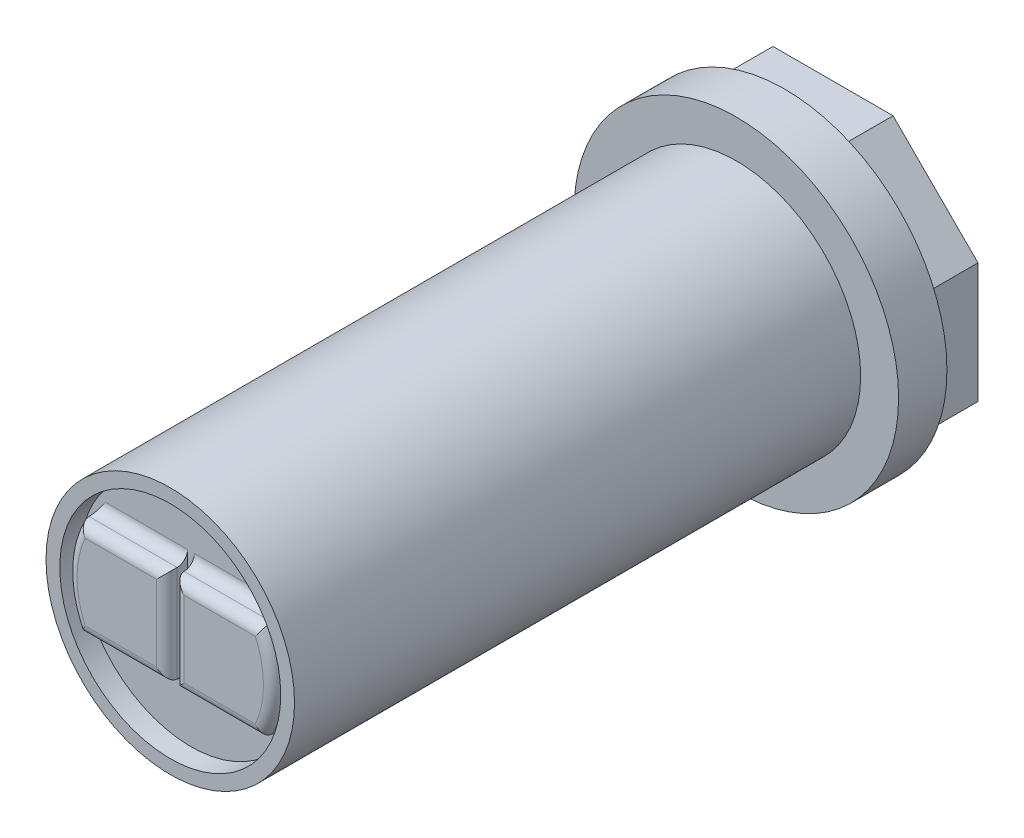
SolidWorks part; units mm, degrees
ref_plane "前视基准面" through (0, 0, 0) normal (0, 0, 1) x (1, 0, 0)
ref_plane "上视基准面" through (0, 0, 0) normal (0, 1, 0) x (1, 0, 0)
ref_plane "右视基准面" through (0, 0, 0) normal (1, 0, 0) x (0, 0, -1)
sketch "草图1" plane through (0, 0, 0) normal (0, 0, 1) x (1, 0, 0)
  circle A0 centre (0, 0) radius 9
  dimension "D1" = 18
extrude "凸台-拉伸1" add sketch "草图1" along normal blind 48
sketch "草图2" plane through (0, 0, 0) normal (0, 0, -1) x (-1, 0, 0)
  line L1 (-10.5, 4.3492) -> (-10.5, -4.3492)
  line L2 (-10.5, -4.3492) -> (-4.3492, -10.5)
  line L3 (-4.3492, -10.5) -> (4.3492, -10.5)
  line L4 (4.3492, -10.5) -> (10.5, -4.3492)
  line L5 (10.5, -4.3492) -> (10.5, 4.3492)
  line L6 (10.5, 4.3492) -> (4.3492, 10.5)
  line L7 (4.3492, 10.5) -> (-4.3492, 10.5)
  line L8 (-4.3492, 10.5) -> (-10.5, 4.3492)
  circle A0 centre (0, 0) radius 10.5 construction
  dimension "D1" = 21
extrude "凸台-拉伸2" add sketch "草图2" against normal blind 3.5
sketch "草图3" plane through (0, 0, 3.5) normal (0, 0, 1) x (1, 0, 0)
  circle A0 centre (0, 0) radius 11.75
  dimension "D1" = 23.5
extrude "凸台-拉伸3" add sketch "草图3" along normal blind 3.5
sketch "草图4" plane through (0, 0, 48) normal (0, 0, 1) x (1, 0, 0)
  line L0 (6.6332, -3.5) -> (0.25, -3.5)
  line L1 (0, 0) -> (-2.8886, 0) construction
  line L2 (6.6332, 3.5) -> (0.25, 3.5)
  line L3 (0.25, -3.5) -> (0.25, 3.5)
  line L4 (0, 0) -> (0, -3.2237) construction
  line L5 (-0.25, -3.5) -> (-0.25, 3.5)
  line L6 (-0.25, -3.5) -> (-6.6332, -3.5)
  line L7 (-0.25, 3.5) -> (-6.6332, 3.5)
  circle A0 centre (0, 0) radius 8
  circle A1 centre (0, 0) radius 9 construction
  arc A2 (6.6332, -3.5) -> (6.6332, 3.5) centre (0, 0) ccw
  arc A3 (-6.6332, 3.5) -> (-6.6332, -3.5) centre (0, 0) ccw
  dimension "D1" = 1
  dimension "D2" = 0.5
  dimension "D3" = 7
  dimension "D4" = 0.5
extrude "切除-拉伸1" cut sketch "草图4" against normal blind 1.5
fillet "圆角1" radius 0.75 12 edges at (-3.4416, 3.5, 46.5) (-3.4416, -3.5, 48) (-7.5, 0, 48) (-0.25, 0, 48) (0.25, 0, 48) (3.4416, -3.5, 48) (7.5, 0, 48) (3.4416, 3.5, 48) (-3.4416, -3.5, 46.5) (3.4416, -3.5, 46.5) (3.4416, 3.5, 46.5) (-3.4416, 3.5, 48)
